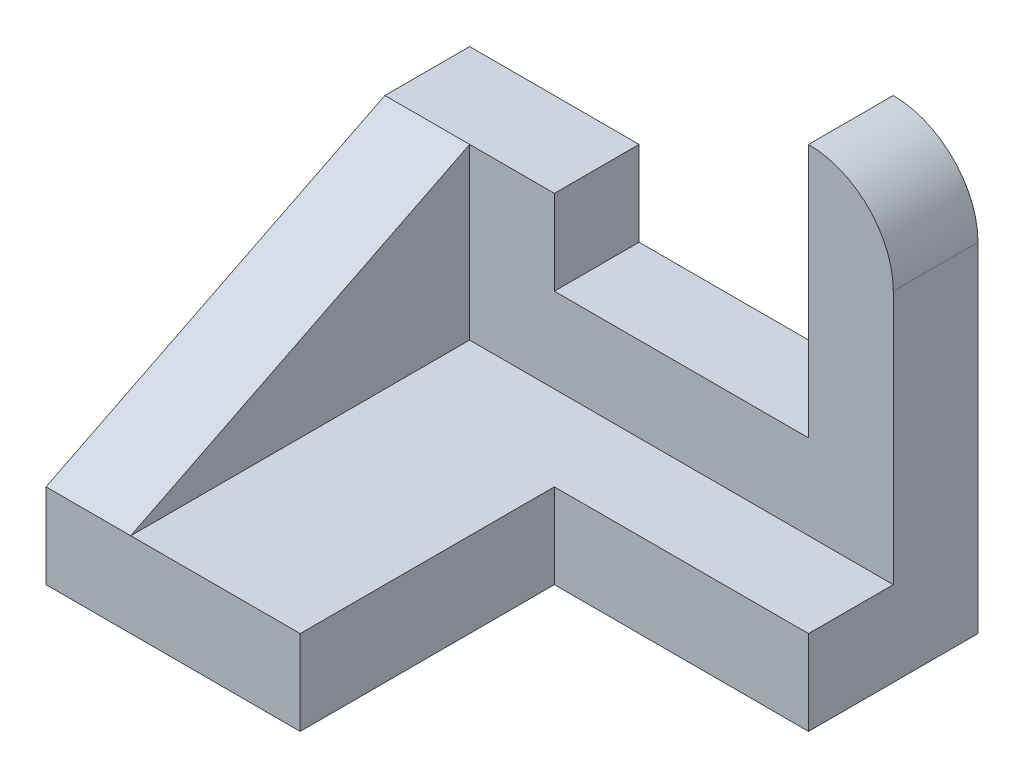
SolidWorks part; units mm, degrees
note: The reader was unsure of these and kept them because the rebuilt part matched: shared geometry of "Sketch1<5>", "Sketch1<6>", "Sketch1<7>".
ref_plane "Front Plane" through (0, 0, 0) normal (0, 0, 1) x (1, 0, 0)
ref_plane "Top Plane" through (0, 0, 0) normal (0, 1, 0) x (1, 0, 0)
ref_plane "Right Plane" through (0, 0, 0) normal (1, 0, 0) x (0, 0, -1)
sketch "Sketch1" plane through (0, 0, 0) normal (0, 0, 1) x (1, 0, 0)
  line L0 (0, 0) -> (0, 762)
  line L1 (0, 762) -> (508, 762)
  line L2 (508, 762) -> (508, 508)
  line L3 (508, 508) -> (1270, 508)
  line L4 (1270, 508) -> (1270, 1270)
  line L5 (0, 0) -> (1524, 0)
  line L6 (1524, 0) -> (1524, 1016)
  line L7 (0, 254) -> (1524, 254)
  line L8 (254, 762) -> (254, 254)
  line L9 (762, 254) -> (762, 0)
  arc A0 (1270, 1270) -> (1524, 1016) centre (1270, 1016) cw
  point P14 (762, 127)
  dimension "D8" = 254
  dimension "D1" = 508
  dimension "D2" = 1524
  dimension "D3" = 254
  dimension "D4" = 254
  dimension "D5" = 762
  dimension "D6" = 1270
  dimension "D7" = 254
  dimension "D9" = 762
extrude "Boss-Extrude1" add sketch "Sketch1" along normal blind 1270 contours L9 L7 L0 L5
extrude "Boss-Extrude2" add sketch "Sketch1<5>" along normal blind 508 contours L7 L9 L5 L6
sketch "Sketch1<5>" plane through (0, 0, 0) normal (0, 0, 1) x (1, 0, 0) same geometry as "Sketch1"
extrude "Boss-Extrude3" add sketch "Sketch1<6>" along normal blind 254 contours A0 L4 L3 L2 L1 L8 L7 L6
sketch "Sketch1<6>" plane through (0, 0, 0) normal (0, 0, 1) x (1, 0, 0) same geometry as "Sketch1"
extrude "Boss-Extrude4" add sketch "Sketch1<7>" along normal blind 1270 contours L8 L1 L0 L7
sketch "Sketch1<7>" plane through (0, 0, 0) normal (0, 0, 1) x (1, 0, 0) same geometry as "Sketch1"
sketch "Sketch2" plane through (254, 0, 0) normal (1, 0, 0) x (0, 0, -1)
  line L0 (-254, 762) -> (-1270, 254)
extrude "Cut-Extrude1" cut sketch "Sketch2" against normal blind 254 and the other way through all flip side to cut
